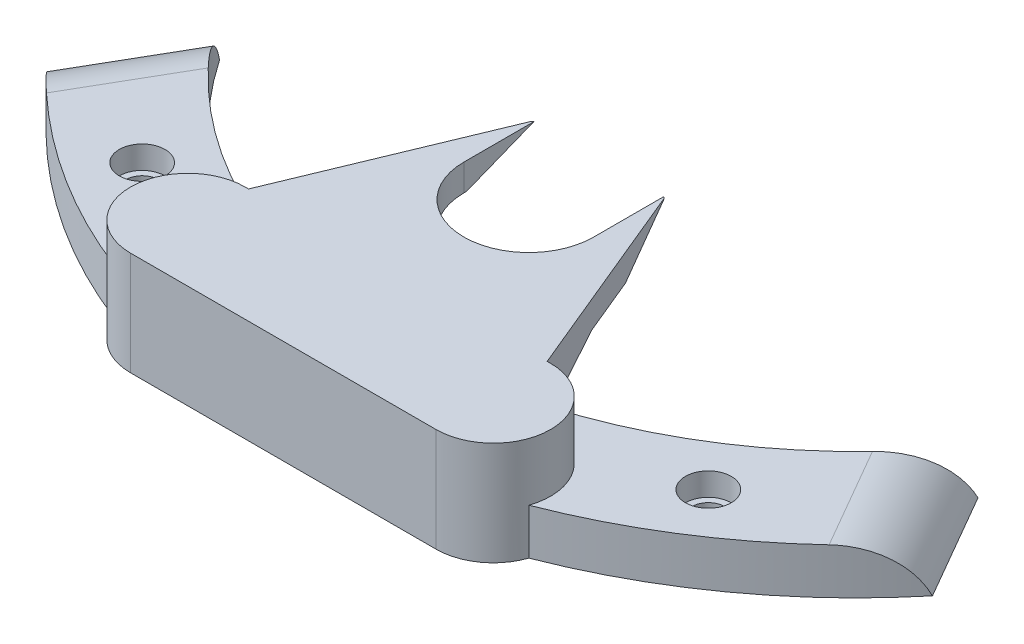
SolidWorks part; units mm, degrees
ref_plane "Front Plane" through (0, 0, 0) normal (0, 0, 1) x (1, 0, 0)
ref_plane "Top Plane" through (0, 0, 0) normal (0, 1, 0) x (1, 0, 0)
ref_plane "Right Plane" through (0, 0, 0) normal (1, 0, 0) x (0, 0, -1)
sketch "Sketch1" plane through (0, 0, 0) normal (0, 1, 0) x (1, 0, 0)
  line L0 (-20, 0) -> (20, 0) construction
  line L1 (-20, 7.5) -> (20, 7.5)
  line L2 (20, -7.5) -> (-20, -7.5)
  circle A0 centre (20, 0) radius 7.5
  circle A1 centre (-20, 0) radius 7.5
  point P4 (0, 0)
  dimension "D1" = 40
  dimension "D2" = 15
extrude "Boss-Extrude1" add sketch "Sketch1" along normal blind 13.57 contours A0 | A1 A0 L1 | A1 L2 A0 | A1 region at (0, 0, 0) region at (-20, 0, 0) region at (20, 0, 0)
ref_plane "Plane1" through (0, 13.57, 0) normal (0, -1, 0) x (-1, 0, 0)
sketch "Sketch3" plane through (0, 13.57, 0) normal (0, -1, 0) x (-1, 0, 0)
  line L0 (0, 0) -> (0, 21.3454) construction
  line L1 (0, 10) -> (0, 7.5) construction
  line L2 (29.0391, 7.5) -> (-29.0391, 7.5)
  line L3 (23.9129, -0.4221) -> (0, 57.3087) construction
  line L4 (-35.3553, 24.6447) -> (35.3553, 24.6447) construction
  line L5 (-35.3553, 24.6447) -> (-35.3553, 95.3553) construction
  line L6 (-35.3553, 95.3553) -> (35.3553, 95.3553) construction
  line L7 (35.3553, 24.6447) -> (35.3553, 95.3553) construction
  line L8 (-35.3553, 24.6447) -> (35.3553, 95.3553) construction
  line L9 (-35.3553, 95.3553) -> (35.3553, 24.6447) construction
  line L10 (0, 57.3087) -> (-24.0511, -0.7557) construction
  line L11 (-8.5, 24.6447) -> (-8.5, 33.8098)
  line L12 (8.5, 24.6447) -> (8.5, 33.8098)
  line L13 (22.989, -0.8048) -> (0, 54.6956)
  line L14 (0, 54.6956) -> (-23.1272, -1.1384)
  circle A0 centre (0, 60) radius 50 construction
  circle A1 centre (0, 24.6447) radius 7.5 construction
  circle A2 centre (0, 24.6447) radius 12.5
  circle A3 centre (0, 24.6447) radius 8.5
  point P2 (0, 10)
  point P4 (0, 10)
  point P27 (18.1786, 13.4217)
  point P28 (-18.1786, 13.4217)
  point P33 (0, 7.5)
  dimension "D2" = 100
  dimension "D3" = 5
  dimension "D5" = 15
  dimension "D4" = 45
  dimension "D6" = 1
  dimension "D7" = 1
extrude "Boss-Extrude3" add sketch "Sketch3" along normal blind 3.5 contours A2 L14 L2 L13 | A3 L11 A2 L14 L13 L12 region at (0, 13.57, -7.9264) region at (0, 13.57, -12.4755)
sketch "Sketch4" plane through (0, 0, 0) normal (1, 0, 0) x (0, 0, -1)
  line L0 (7.5, 10.07) -> (7.5, 7.17)
  line L1 (7.5, 13.57) -> (7.5, 0) construction
  line L2 (7.5, 10.07) -> (17.5, 10.07)
  line L3 (33.5716, 10.07) -> (7.5, 10.07) construction
  line L4 (7.5, 7.17) -> (17.5, 10.07)
  dimension "D1" = 2.9
  dimension "D2" = 10
extrude "Boss-Extrude4" add sketch "Sketch4" along normal blind 26 and the other way blind 27
sketch "Sketch5" plane through (0, 10.07, 0) normal (0, 1, 0) x (1, 0, 0)
  line L0 (-19.5491, 7.5) -> (-15.4069, 17.5) construction
  line L1 (-15.4069, 17.5) -> (-27, 17.5) construction
  line L2 (-27, 17.5) -> (-27, 7.5) construction
  line L3 (-27, 7.5) -> (-20, 7.5) construction
  line L4 (-20, 7.5) -> (-19.5491, 7.5) construction
  line L5 (15.4069, 17.5) -> (19.5491, 7.5) construction
  line L6 (19.5491, 7.5) -> (20, 7.5) construction
  line L7 (20, 7.5) -> (26, 7.5) construction
  line L8 (26, 7.5) -> (26, 17.5) construction
  line L9 (26, 17.5) -> (15.4069, 17.5) construction
  line L10 (-19.5491, 7.5) -> (-15.4069, 17.5)
  line L11 (-15.4069, 17.5) -> (-27, 17.5)
  line L12 (-27, 17.5) -> (-27, 7.5)
  line L13 (-27, 7.5) -> (-20, 7.5)
  line L14 (-20, 7.5) -> (-19.5491, 7.5)
  line L15 (15.4069, 17.5) -> (19.5491, 7.5)
  line L16 (19.5491, 7.5) -> (20, 7.5)
  line L17 (20, 7.5) -> (26, 7.5)
  line L18 (26, 7.5) -> (26, 17.5)
  line L19 (26, 17.5) -> (15.4069, 17.5)
  line L21 (4.6048, 17.5) -> (-4.6048, 17.5)
  line L22 (4.6048, 17.5) -> (-4.6048, 17.5)
  arc A1 (-4.6048, 17.5) -> (4.6048, 17.5) centre (0, 24.6447) ccw
  arc A2 (-4.6048, 17.5) -> (4.6048, 17.5) centre (0, 24.6447) ccw
  dimension "D1" = 0
extrude "Cut-Extrude1" cut sketch "Sketch5" against normal through all both
sketch "Sketch6" plane through (0, 0, 0) normal (1, 0, 0) x (0, 0, -1)
  line L0 (25, 10.07) -> (33.8098, 13.57)
  line L1 (33.8098, 13.57) -> (25, 13.57)
  line L2 (33.5716, 13.57) -> (7.5, 13.57) construction
  line L3 (25, 13.57) -> (25, 10.07)
  line L4 (25, 10.07) -> (32.5042, 4.5383)
  line L5 (32.5042, 4.5383) -> (33.8098, 6.6469)
  line L6 (33.8098, 6.6469) -> (33.8098, 13.57)
  line L7 (17.5, 10.07) -> (17.5, 16.0325) construction
  line L8 (25, 13.57) -> (17.5, 13.57)
  line L9 (33.5716, 10.07) -> (17.5, 10.07) construction
  point P3 (25, 10.07)
  point P15 (33.8098, 13.57)
  dimension "D1" = 7.5
extrude "Cut-Extrude2" cut sketch "Sketch6" against normal through all both and the other way through all contours L5 L6 L0 L4 region at (0, 9.27, -30.7539)
sketch "Sketch7" plane through (0, 0, 0) normal (0, 1, 0) x (1, 0, 0)
  line L0 (-1.0996, -7.5) -> (1.0996, -7.5)
  line L1 (20, -7.5) -> (-20, -7.5) construction
  line L2 (49.6485, 33.8098) -> (57.7945, 19.7005)
  line L3 (0, 67.5) -> (0, 57.5141) construction
  line L4 (8.5, 33.8098) -> (49.6485, 33.8098) construction
  line L5 (-49.6485, 33.8098) -> (-57.7945, 19.7005)
  circle A0 centre (0, 67.5) radius 75
  circle A1 centre (0, 67.5) radius 60
  point P7 (0, -7.5)
  dimension "D1" = 150
  dimension "D3" = 30
  dimension "D2" = 15
extrude "Boss-Extrude5" add sketch "Sketch7" along normal blind 6 contours A1 L5 A0 L2 region at (52.6585, 0, -26.1414)
fillet "Fillet1" radius 10 2 edges at (-53.7215, 6, -26.7551) (53.7215, 6, -26.7551)
sketch "Sketch8" plane through (0, 6, 0) normal (0, 1, 0) x (1, 0, 0)
  line L0 (33.2234, 17.538) -> (40.9053, 4.637) construction
  line L1 (26.7689, 2.7316) -> (47.3599, 19.4434) construction
  line L2 (51.2363, 12.7292) -> (43.4834, 26.1577) construction
  line L3 (0, -7.8365) -> (0, 7.8365) construction
  arc A0 (0, 7.5) -> (43.4834, 26.1577) centre (0, 67.5) ccw construction
  arc A1 (27.0936, -2.4352) -> (51.2363, 12.7292) centre (0, 67.5) ccw construction
  circle A2 centre (37.0644, 11.0875) radius 2.15
  circle A3 centre (37.0644, 11.0875) radius 3
  circle A4 centre (-37.0644, 11.0875) radius 2.15
  circle A5 centre (-37.0644, 11.0875) radius 3
  point P12 (37.0644, 11.0875)
  dimension "D1" = 0.85
  dimension "D2" = 4.3
extrude "Cut-Extrude3" cut sketch "Sketch8" against normal through all contours A2 | A4 region at (37.0644, 6, -11.0875)
extrude "Cut-Extrude4" cut sketch "Sketch8<4>" against normal blind 3
sketch "Sketch8<4>" plane through (0, 6, 0) normal (0, 1, 0) x (1, 0, 0) same geometry as "Sketch8"
